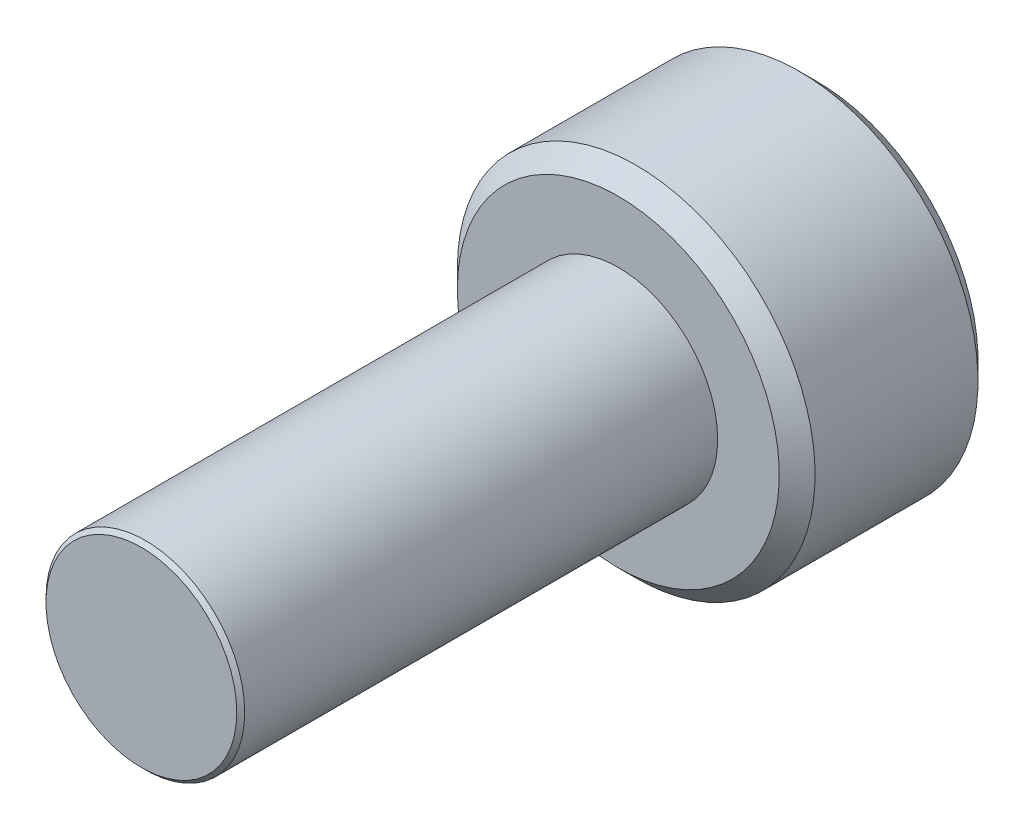
SolidWorks part; units mm, degrees
ref_plane "Front Plane" through (0, 0, 0) normal (0, 0, 1) x (1, 0, 0)
ref_plane "Top Plane" through (0, 0, 0) normal (0, 1, 0) x (1, 0, 0)
ref_plane "Right Plane" through (0, 0, 0) normal (1, 0, 0) x (0, 0, -1)
sketch "Sketch1" plane through (0, 0, 0) normal (0, 0, 1) x (1, 0, 0)
  circle A0 centre (0, 0) radius 1.25
  dimension "OD" = 2.5
extrude "Extrude1" add sketch "Sketch1" against normal blind 6
sketch "Sketch2" plane through (0, 0, 0) normal (0, 0, 1) x (1, 0, 0)
  circle A0 centre (0, 0) radius 1.25 construction
  circle A1 centre (0, 0) radius 1.25
curve "Helix/Spiral1" pitch 0.45 height 6.45 radius 1.25 centre (0, 0, 0) axis (0, 0, -1) start towards (0, 1, 0) parameters "pitch"=0.45
sketch "Sketch3" plane through (0, 0, 0) normal (1, 0, 0) x (0, 0, -1)
  line L0 (-0.3937, 1.25) -> (-0.225, 0.9577)
  line L1 (-0.225, 0.9577) -> (-0.1688, 0.9577)
  line L2 (-0.1688, 0.9577) -> (0, 1.25)
  line L3 (-0.3937, 1.25) -> (0, 1.25)
  line L4 (-0.1969, 1.25) -> (-0.1969, 0.9577) construction
  line L5 (-0.3094, 1.1039) -> (-0.0844, 1.1039) construction
  line L6 (0, 1.25) -> (0, -1.25) construction
  dimension "D1" = 0.0563
  dimension "D2" = 0.225
  dimension "D3" = 60
sweep "Cut-Sweep1" cut profiles "Sketch3" path "Helix/Spiral1" align with end faces yes
sketch "Sketch4" plane through (0, 0, 0) normal (1, 0, 0) x (0, 0, -1)
  line L0 (0.3825, 1.25) -> (0, 0.7037)
  line L1 (0, 0.7037) -> (0, 1.25)
  line L2 (0.3825, 1.25) -> (0, 1.25)
  line L3 (-0.3937, 1.25) -> (0, 1.25) construction
  line L4 (0, 0) -> (7.0209, 0) construction
  dimension "D1" = 55
  dimension "D2" = 0.254
revolve "Cut-Revolve1" cut sketch "Sketch4" angle 360 about L4
sketch "Sketch6" plane through (0, 0, -6) normal (0, 0, -1) x (-1, 0, 0)
  circle A0 centre (0, 0) radius 2.25
  dimension "head dia" = 4.5
extrude "Extrude2" add sketch "Sketch6" along normal blind 2.5
sketch "Sketch7" plane through (0, 0, -8.5) normal (0, 0, -1) x (-1, 0, 0)
  line L1 (0, 1.1547) -> (-1, 0.5774)
  line L2 (-1, 0.5774) -> (-1, -0.5774)
  line L3 (-1, -0.5774) -> (0, -1.1547)
  line L4 (0, -1.1547) -> (1, -0.5774)
  line L5 (1, -0.5774) -> (1, 0.5774)
  line L6 (1, 0.5774) -> (0, 1.1547)
  circle A0 centre (0, 0) radius 1 construction
  dimension "hex dia" = 2
extrude "Cut-Extrude1" cut sketch "Sketch7" against normal blind 1.5
sketch "Sketch8" plane through (0, 0, -8.5) normal (0, 0, -1) x (-1, 0, 0)
  circle A0 centre (0, 0) radius 1.1547
extrude "Cut-Extrude2" cut sketch "Sketch8" against normal through all draft 45
chamfer "Chamfer1" distance 0.225 angle 45 2 edges at (-2.25, 0, -8.5) (-2.25, 0, -6)
sketch "Sketch10" plane through (0, 0, -6) normal (0, 0, 1) x (1, 0, 0)
  circle A1 centre (0, 0) radius 1.25
  circle A2 centre (0, 0) radius 1.25
  dimension "D1" = 0
ref_plane "Plane1" through (0, 0, 0) normal (0, 0, 1) x (1, 0, 0)
extrude "partial thread" add sketch "Sketch10" along normal up to surface (6 mm away) separate body up to plane "Plane1"
chamfer "Chamfer2" distance 0.05 angle 45 1 edges at (1.25, 0, 0)
combine bodies "Combine1" operation type add bodies to combine 107 108
sketch "Sketch9" plane through (0, 0, 0) normal (1, 0, 0) x (0, 0, -1)
  line L0 (0, 1.25) -> (0, -1.25) construction
  line L1 (1.125, 1.25) -> (1.125, -1.25) construction
  dimension "D1" = 1.125
equation "\"D3@Helix/Spiral1\" = \"screw length@Extrude1\"+\"pitch@Helix/Spiral1\""
equation "\"D1@Sketch3\" = \"pitch@Helix/Spiral1\"*.125"
equation "\"D2@Sketch3\" = \"pitch@Helix/Spiral1\"*.5"
equation "\"D1@Cut-Extrude1\" = \"hex dia@Sketch7\"*.75"
equation "\"D1@Chamfer1\" = \"head dia@Sketch6\"*.05"
equation "\"D1@Sketch9\" = \"pitch@Helix/Spiral1\"*2.5"
equation "\"D1@Chamfer2\"=\"OD@Sketch1\"*.02"
